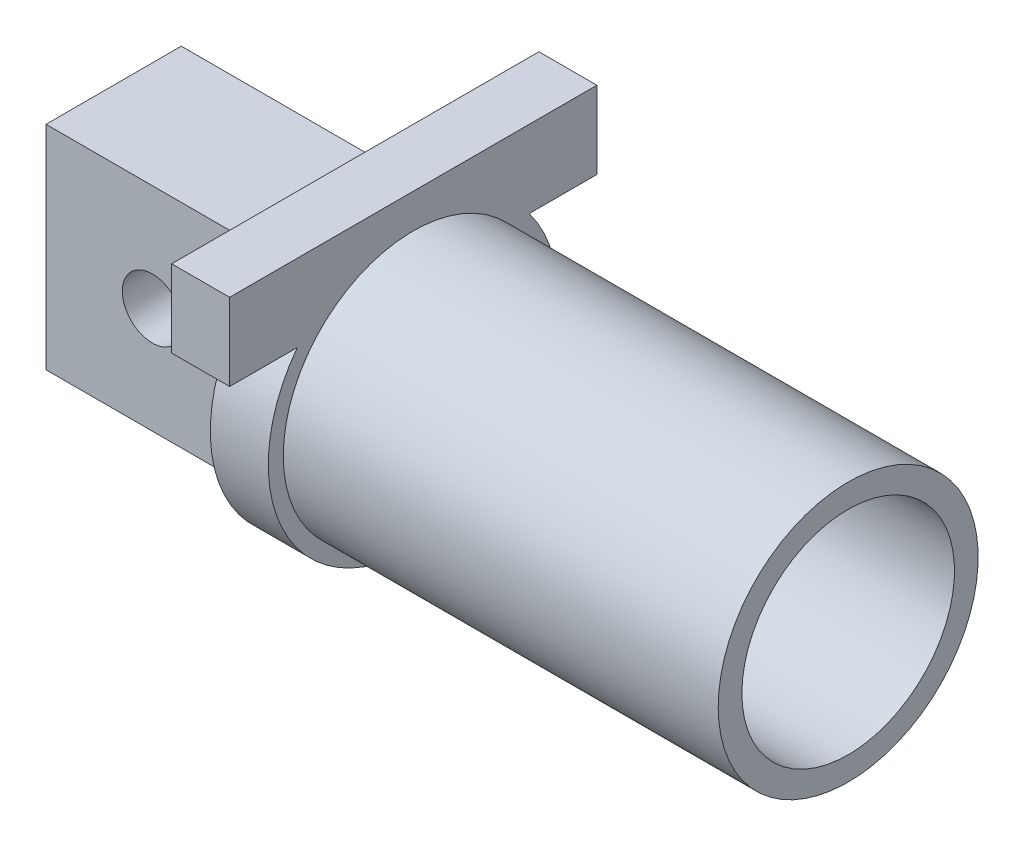
SolidWorks part; units mm, degrees
ref_plane "Front Plane" through (0, 0, 0) normal (0, 0, 1) x (1, 0, 0)
ref_plane "Top Plane" through (0, 0, 0) normal (0, 1, 0) x (1, 0, 0)
ref_plane "Right Plane" through (0, 0, 0) normal (1, 0, 0) x (0, 0, -1)
sketch "Stem Sketch" plane through (0, 0, 0) normal (0, 0, 1) x (1, 0, 0)
  line L0 (-3000, 0) -> (3000, 0) construction
  line L1 (14, 0) -> (14, 15)
  line L2 (14, 15) -> (20, 15)
  line L3 (20, 15) -> (20, 13.45)
  line L4 (20, 13.45) -> (65, 13.45)
  line L5 (65, 13.45) -> (65, 11)
  line L6 (65, 11) -> (30, 11)
  line L7 (30, 11) -> (30, 0)
  line L8 (30, 0) -> (14, 0)
revolve "Stem" add sketch "Stem Sketch" angle 360 about L0
ref_axis "Engine Axis" through (68.8, 0, 0) along (-1, 0, 0)
sketch "Tongue Sketch" plane through (0, 0, 0) normal (0, 0, 1) x (1, 0, 0)
  line L0 (-11, -11) -> (16, -11)
  line L1 (16, -11) -> (16, 11)
  line L2 (16, 11) -> (-11, 11)
  line L3 (-11, 11) -> (-11, -11)
extrude "Tongue" add sketch "Tongue Sketch" along normal mid plane 14
sketch "Pad Sketch" plane through (0, 0, 0) normal (0, 0, 1) x (1, 0, 0)
  line L0 (14, 9) -> (20, 9)
  line L1 (20, 9) -> (20, 17)
  line L2 (20, 17) -> (14, 17)
  line L3 (14, 17) -> (14, 9)
extrude "Switch Pad" add sketch "Pad Sketch" along normal mid plane 38
sketch "Pin Hole Sketch" plane through (0, 0, 0) normal (0, 0, 1) x (1, 0, 0)
  circle A0 centre (0, 0) radius 3.1
extrude "Pin Hole" cut sketch "Pin Hole Sketch" against normal mid plane 20
